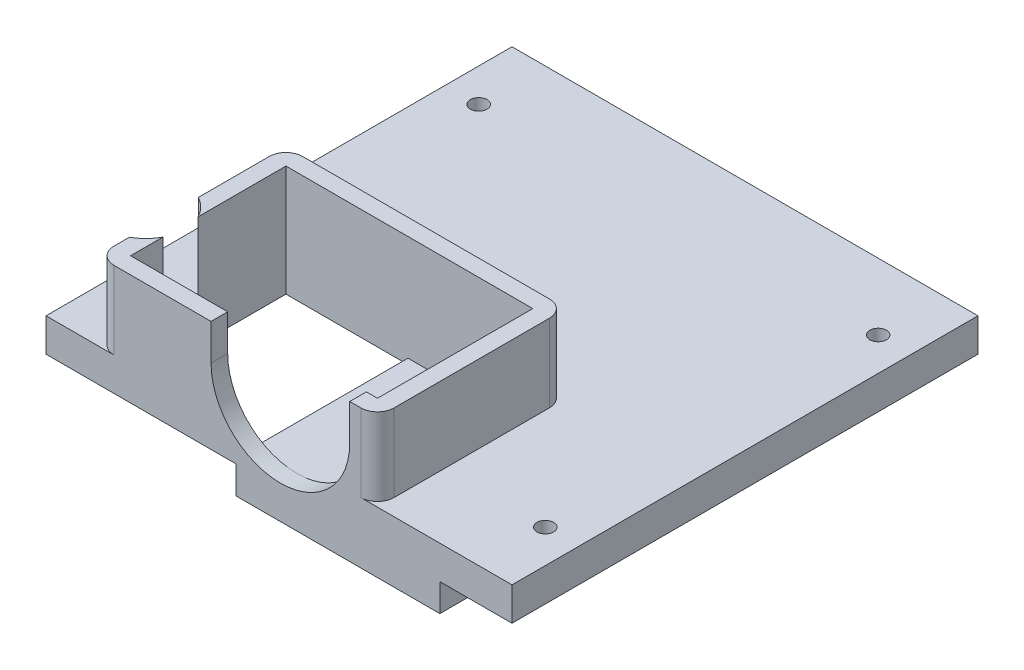
SolidWorks part; units mm, degrees
material "PVB"
ref_plane "Front Plane" through (0, 0, 0) normal (0, 0, 1) x (1, 0, 0)
ref_plane "Top Plane" through (0, 0, 0) normal (0, 1, 0) x (1, 0, 0)
ref_plane "Right Plane" through (0, 0, 0) normal (1, 0, 0) x (0, 0, -1)
sketch "Sketch1" plane through (0, 0, 0) normal (0, 1, 0) x (1, 0, 0)
  line L1 (0, 0) -> (84, 0)
  line L2 (0, 0) -> (0, 84)
  line L3 (0, 84) -> (84, 84)
  line L4 (84, 0) -> (84, 84)
  dimension "D1" = 84
  dimension "D2" = 84
extrude "Boss-Extrude1" add sketch "Sketch1" along normal blind 6
sketch "Sketch2" plane through (0, 6, 0) normal (0, 1, 0) x (1, 0, 0)
  line L0 (84, 84) -> (0, 84) construction
  line L1 (0, 84) -> (0, 0) construction
  line L2 (0, 0) -> (84, 0) construction
  line L3 (84, 0) -> (84, 84) construction
  circle A0 centre (6, 72) radius 1.5
  circle A1 centre (6, 12) radius 1.5
  circle A2 centre (78, 12) radius 1.5
  circle A3 centre (78, 72) radius 1.5
  dimension "D1" = 3
  dimension "D2" = 3
  dimension "D3" = 3
  dimension "D4" = 3
  dimension "D6" = 6
  dimension "D7" = 12
  dimension "D8" = 6
  dimension "D9" = 6
  dimension "D10" = 12
  dimension "D11" = 6
  dimension "D5" = 12
  dimension "D12" = 12
extrude "Cut-Extrude1" cut sketch "Sketch2" against normal through all
ref_plane "Plane1" through (0, 0, -42) normal (0, 0, 1) x (1, 0, 0)
sketch "Sketch4" plane through (0, 6, 0) normal (0, 1, 0) x (1, 0, 0)
  line L0 (3, 21) -> (3, 9)
  line L1 (3, 9) -> (13, 9)
  line L2 (13, 15) -> (8, 21)
  line L3 (3, 21) -> (8, 21)
  line L4 (8, 21) -> (13, 15)
  line L5 (13, 15) -> (13, 9)
  line L6 (0, 84) -> (0, 0) construction
  line L7 (0, 0) -> (84, 0) construction
  circle A0 centre (6, 12) radius 1.5
  circle A1 centre (6, 12) radius 1.5 construction
  dimension "D1" = 3
  dimension "D2" = 9
  dimension "D3" = 12
  dimension "D4" = 10
  dimension "D5" = 6
  dimension "D6" = 5
ref_plane "Plane2" through (42, 0, 0) normal (-1, 0, 0) x (0, 0, 1)
sketch "Sketch5" plane through (0, 6, 0) normal (0, 1, 0) x (1, 0, 0)
  line L0 (9.25, 34) -> (9.25, 0)
  line L1 (9.25, 34) -> (59.75, 34)
  line L2 (9.25, 0) -> (59.75, 0)
  line L3 (59.75, 34) -> (59.75, 0)
  line L4 (9.25, 34) -> (59.75, 0) construction
  line L5 (9.25, 0) -> (59.75, 34) construction
  line L6 (42, 3.3) -> (42, -3.3) construction
  line L12 (0, 0) -> (84, 0) construction
  point P1 (34.5, 17)
  dimension "D1" = 50.5
  dimension "D2" = 34
  dimension "D3" = 7.5
extrude "Boss-Extrude2" add sketch "Sketch5" along normal blind 22
sketch "Sketch6" plane through (0, 28, 0) normal (0, 1, 0) x (1, 0, 0)
  line L14 (56.75, 31) -> (12.25, 31)
  line L15 (12.25, 31) -> (12.25, 3)
  line L16 (12.25, 3) -> (56.75, 3)
  line L17 (56.75, 3) -> (56.75, 31)
  line L18 (56.75, 31) -> (12.25, 31)
  line L19 (12.25, 31) -> (12.25, 3)
  line L20 (12.25, 3) -> (56.75, 3)
  line L21 (56.75, 3) -> (56.75, 31)
  dimension "D1" = 3
extrude "Cut-Extrude5" cut sketch "Sketch6" against normal blind 25
fillet "Fillet1" radius 3 4 edges at (9.25, 17, -34) (59.75, 17, 0) (59.75, 17, -34) (9.25, 17, 0)
sketch "Sketch8" plane through (0, 0, 0) normal (0, 0, 1) x (1, 0, 0)
  line L1 (0, 0) -> (84, 0) construction
  line L3 (59.75, 28) -> (59.75, 6) construction
  circle A0 centre (42.25, 13.5) radius 12.5
  dimension "D2" = 25
  dimension "D1" = 17.5
  dimension "D3" = 13.5
extrude "Cut-Extrude6" cut sketch "Sketch8" against normal blind 10
sketch "Sketch9" plane through (0, 0, 0) normal (0, 0, 1) x (1, 0, 0)
  line L0 (0, 0) -> (84, 0) construction
  line L1 (0, 28) -> (84, 28)
  line L2 (0, 28) -> (0, 20)
  line L3 (0, 20) -> (84, 20)
  line L4 (84, 28) -> (84, 20)
  line L5 (84, 6) -> (84, 0) construction
  line L6 (0, 6) -> (0, 0) construction
  line L7 (12.25, 28) -> (56.75, 28) construction
  dimension "D1" = 20
extrude "Cut-Extrude7" cut sketch "Sketch9" against normal through all both and the other way through all
sketch "Sketch11" plane through (0, 0, 0) normal (0, -1, 0) x (1, 0, 0)
  line L0 (3, -9) -> (13, -9)
  line L1 (13, -9) -> (13, -15)
  line L2 (13, -15) -> (8, -21)
  line L3 (8, -21) -> (3, -21)
  line L4 (3, -21) -> (3, -9)
extrude "Cut-Extrude8" cut sketch "Sketch11" against normal blind 3
mirror "Mirror1" about plane through (0, 0, -42) normal (0, 0, 1) of "Cut-Extrude8" second plane through (42, 0, 0) second plane normal (-1, 0, 0)
sketch "Sketch13" plane through (0, 20, 0) normal (0, 1, 0) x (1, 0, 0)
  line L12 (52.9271, 0) -> (56.75, 0)
  line L13 (59.75, 3) -> (59.75, 31)
  line L14 (56.75, 34) -> (12.25, 34)
  line L15 (9.25, 31) -> (9.25, 3)
  line L16 (12.25, 0) -> (31.5729, 0)
  line L17 (12.25, 0) -> (31.5729, 0)
  line L18 (31.5729, 0) -> (31.5729, 3)
  line L19 (31.5729, 0) -> (31.5729, 3)
  line L20 (31.5729, 3) -> (12.25, 3)
  line L21 (31.5729, 3) -> (12.25, 3)
  line L22 (12.25, 3) -> (12.25, 31)
  line L23 (12.25, 3) -> (12.25, 31)
  line L24 (52.9271, 0) -> (56.75, 0)
  line L25 (59.75, 3) -> (59.75, 31)
  line L26 (56.75, 34) -> (12.25, 34)
  line L27 (9.25, 31) -> (9.25, 3)
  line L37 (12.25, 31) -> (56.75, 31)
  line L38 (12.25, 31) -> (56.75, 31)
  line L39 (56.75, 31) -> (56.75, 3)
  line L40 (56.75, 31) -> (56.75, 3)
  line L41 (56.75, 3) -> (52.9271, 3)
  line L42 (56.75, 3) -> (52.9271, 3)
  line L43 (52.9271, 3) -> (52.9271, 0)
  line L44 (52.9271, 3) -> (52.9271, 0)
  circle A0 centre (6, 12) radius 1.5 construction
  circle A1 centre (6, 12) radius 1.5
  circle A2 centre (6, 12) radius 7
  arc A11 (56.75, 0) -> (59.75, 3) centre (56.75, 3) ccw
  arc A12 (56.75, 0) -> (59.75, 3) centre (56.75, 3) ccw
  arc A13 (59.75, 31) -> (56.75, 34) centre (56.75, 31) ccw
  arc A14 (59.75, 31) -> (56.75, 34) centre (56.75, 31) ccw
  arc A15 (12.25, 34) -> (9.25, 31) centre (12.25, 31) ccw
  arc A24 (12.25, 34) -> (9.25, 31) centre (12.25, 31) ccw
  arc A25 (9.25, 3) -> (12.25, 0) centre (12.25, 3) ccw
  arc A26 (9.25, 3) -> (12.25, 0) centre (12.25, 3) ccw
  dimension "D2" = 14
  dimension "D1" = 0
extrude "Cut-Extrude9" cut sketch "Sketch13" against normal up to surface (14 mm away) contours L27 A2 L23 region at (10.6036, 20, -12) up to face at (6, 6, -70.5)
sketch "Sketch14" plane through (0, 0, 0) normal (0, 0, 1) x (1, 0, 0)
  line L0 (29.75, 13.5) -> (29.75, 20)
  line L1 (31.5729, 20) -> (12.25, 20) construction
  line L2 (29.75, 20) -> (31.5729, 20)
  line L3 (31.5729, 20) -> (29.75, 13.5)
  arc A0 (31.5729, 20) -> (52.9271, 20) centre (42.25, 13.5) ccw construction
extrude "Cut-Extrude10" cut sketch "Sketch14" against normal blind 10
sketch "Sketch15" plane through (0, 0, 0) normal (0, 0, 1) x (1, 0, 0)
  line L0 (54.75, 20) -> (54.75, 13.5)
  line L1 (56.75, 20) -> (52.9271, 20) construction
  line L2 (54.75, 20) -> (52.9271, 20)
  line L3 (52.9271, 20) -> (54.75, 13.5)
  arc A0 (29.75, 13.5) -> (52.9271, 20) centre (42.25, 13.5) ccw construction
extrude "Cut-Extrude11" cut sketch "Sketch15" against normal blind 10
sketch "Sketch17" plane through (0, 0, 0) normal (0, -1, 0) x (1, 0, 0)
  line L0 (9.6667, -9) -> (9.6667, -19)
  line L1 (13, -9) -> (3, -9) construction
  line L2 (8, -21) -> (13, -15) construction
  line L3 (9.6667, -19) -> (13, -15)
  line L4 (13, -15) -> (13, -9)
  line L5 (13, -9) -> (9.6667, -9)
  dimension "D1" = 10
extrude "Boss-Extrude3" add sketch "Sketch17" against normal up to surface (3 mm away) up to face at (7.7, 3, -15.18)
sketch "Sketch18" plane through (0, 3, 0) normal (0, 1, 0) x (1, 0, 0)
  line L8 (35.4677, 3) -> (35.4677, 10)
  line L9 (35.4677, 10) -> (49.0323, 10)
  line L10 (49.0323, 10) -> (49.0323, 3)
  line L11 (49.0323, 3) -> (56.75, 3)
  line L12 (56.75, 3) -> (56.75, 31)
  line L13 (56.75, 31) -> (12.25, 31)
  line L14 (12.25, 31) -> (12.25, 3)
  line L15 (12.25, 3) -> (35.4677, 3)
extrude "Cut-Extrude14" cut sketch "Sketch18" against normal blind 4
sketch "Sketch20" plane through (0, 0, 0) normal (0, -1, 0) x (1, 0, 0)
  line L1 (35.4677, -10) -> (49.0323, -10)
  line L2 (35.4677, -10) -> (35.4677, -3)
  line L3 (35.4677, -3) -> (49.0323, -3)
  line L4 (49.0323, -10) -> (49.0323, -3)
extrude "Cut-Extrude15" cut sketch "Sketch20" against normal blind 4
sketch "Sketch21" plane through (0, 0, 0) normal (0, -1, 0) x (1, 0, 0)
  line L0 (0, 0) -> (84, 0) construction
  line L1 (34.25, 0) -> (71, 0)
  line L2 (34.25, 0) -> (34.25, -37)
  line L3 (34.25, -37) -> (71, -37)
  line L4 (71, 0) -> (71, -37)
  line L5 (71, -15) -> (71, -9) construction
  line L8 (12.25, -3) -> (12.25, -31) construction
  line L9 (12.25, -31) -> (56.75, -31) construction
  dimension "D1" = 22
  dimension "D2" = 6
extrude "Boss-Extrude4" add sketch "Sketch21" along normal blind 5 and the other way blind 1
fillet "Fillet2" radius 5 2 edges at (71, -2.5, -37) (34.25, -2.5, -37)
